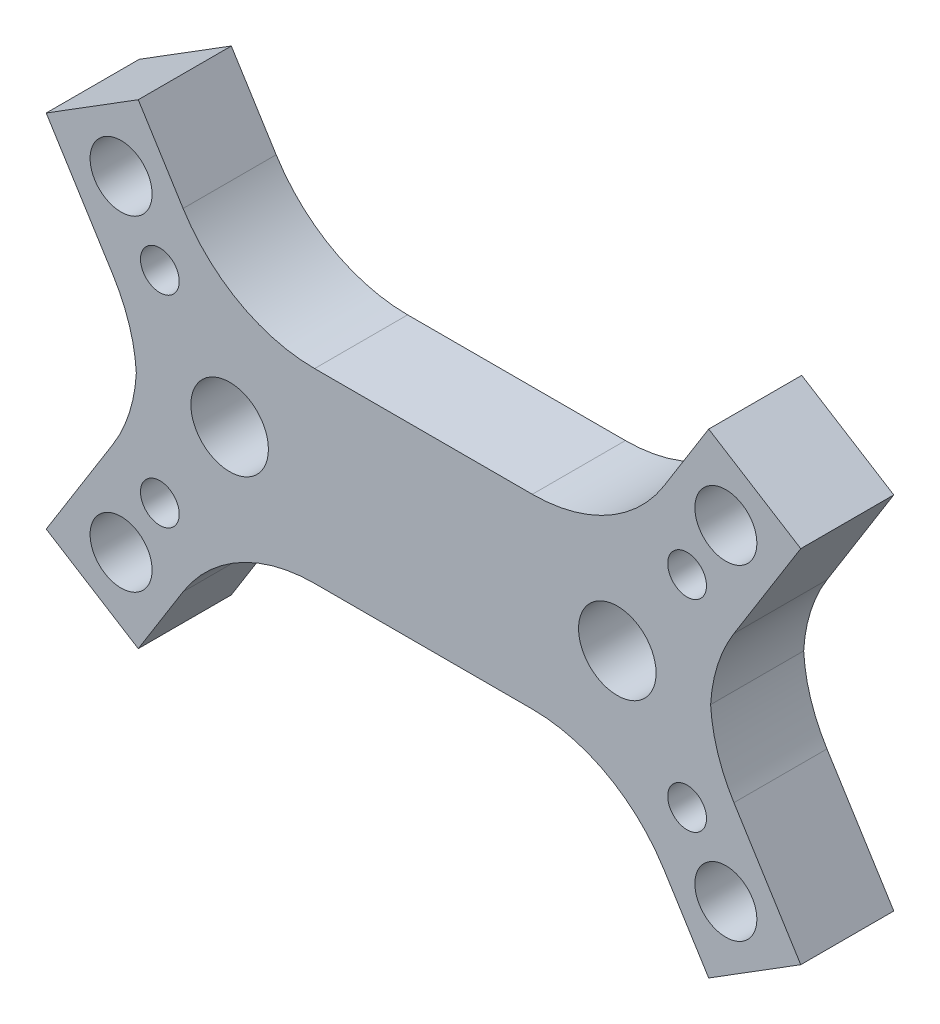
SolidWorks part; units mm, degrees
material "Polyetheretherketone (PEEK)"
ref_plane "Front Plane" through (0, 0, 0) normal (0, 0, 1) x (1, 0, 0)
ref_plane "Top Plane" through (0, 0, 0) normal (0, 1, 0) x (1, 0, 0)
ref_plane "Right Plane" through (0, 0, 0) normal (1, 0, 0) x (0, 0, -1)
ref_plane "Plane1" through (0, 0, 1.2) normal (0, 0, 1) x (1, 0, 0)
sketch "Sketch1" plane through (0, 0, 1.2) normal (0, 0, 1) x (1, 0, 0)
  line L0 (7.4, 2.4) -> (0, 2.4)
  line L1 (0, 2.4) -> (0, 0)
  line L2 (0, 0) -> (7.4, 0)
  line L3 (7.4, 0) -> (7.4, 2.4)
  line L4 (-0.6415, 3.4266) -> (0.6415, 1.3734)
  line L5 (8.1339, 3.5744) -> (6.6661, 1.2256)
  line L6 (0, 1.6581) -> (1.1873, 2.4)
  line L7 (0, 1.6581) -> (-1.1658, 3.5238)
  line L8 (1.1873, 2.4) -> (0.0214, 4.2657)
  line L9 (-1.1658, 3.5238) -> (0.0214, 4.2657)
  line L10 (6.2127, 2.4) -> (7.4, 1.6581)
  line L11 (6.2127, 2.4) -> (7.3786, 4.2657)
  line L12 (7.4, 1.6581) -> (8.5658, 3.5238)
  line L13 (7.3786, 4.2657) -> (8.5658, 3.5238)
  line L14 (0.563, 0.901) -> (0, 0)
  line L15 (7.9999, -0.9601) -> (6.8001, 0.9601)
  line L16 (0, 0.7419) -> (1.1873, 0)
  line L17 (0, 0.7419) -> (-1.1658, -1.1238)
  line L18 (1.1873, 0) -> (0.0214, -1.8657)
  line L19 (-1.1658, -1.1238) -> (0.0214, -1.8657)
  line L20 (6.2127, 0) -> (7.4, 0.7419)
  line L21 (6.2127, 0) -> (7.3786, -1.8657)
  line L22 (7.4, 0.7419) -> (8.5658, -1.1238)
  line L23 (7.3786, -1.8657) -> (8.5658, -1.1238)
  point P7 (0, 2.4)
  point P10 (7.4, 2.4)
  point P22 (0, 0)
  point P25 (7.4, 0)
  dimension "D1" = 2.4
  dimension "D2" = 7.4
  dimension "D3" = 58
  dimension "D4" = 58
  dimension "D5" = 1.4
  dimension "D6" = 2.2
  dimension "D7" = 1.4
  dimension "D8" = 2.2
  dimension "D9" = 58
  dimension "D10" = 58
  dimension "D11" = 2.2
  dimension "D12" = 1.4
  dimension "D13" = 2.2
  dimension "D14" = 1.4
extrude "Boss-Extrude1" add sketch "Sketch1" against normal blind 1.2 contours L9 L7 L1 L0 L8 | L19 L2 L1 | L13 L11 L0 L3 L12 | L21 L23 L22 L3 L2 | L2 L20 L3 L10 L0 L6 L1 | L4 L6 L0 | L1 L6 L4 | L2 | L1 | L20 L2 L15 | L20 L15 L3 | L5 L10 L3 | L0 L10 L5 region at (6.8931, 2.2221, 1.2) region at (7.4535, 3.0969, 1.2) region at (7.2889, 1.9749, 1.2) region at (3.7, 1.2, 1.2) region at (0.5069, 2.2221, 1.2) region at (-0.0535, 3.0969, 1.2) region at (7.4535, -0.6969, 1.2) region at (7.2889, 0.4251, 1.2) region at (0.1111, 1.9749, 1.2) region at (6.8931, 0.1779, 1.2) region at (0.1111, 0.4251, 1.2) region at (-0.0535, -0.6969, 1.2) region at (0.5069, 0.1779, 1.2)
hole_wizard "Hole1" positions "Sketch5" profile "Sketch4" legacy end condition through all
sketch "Sketch5" plane through (0, 0, 1.2) normal (0, 0, 1) x (1, 0, 0)
  point P0 (1.2, 1.2)
  point P1 (6.2, 1.2)
sketch "Sketch4" plane through (1.2, 1.2, 1.2) normal (1, 0, 0) x (0, -1, 0)
  line L0 (0, 0) -> (0, 1.2)
  line L1 (0, 1.2) -> (0.3, 1.2)
  line L2 (0.3, 1.2) -> (0.3, 0.9)
  line L3 (0.3, 0.9) -> (0.5, 0.9)
  line L4 (0.5, 0.9) -> (0.5, 0)
  line L5 (0.5, 0) -> (0, 0)
  line L6 (0, 110) -> (0, -10) construction
  dimension "Diameter" = 0.6
  dimension "Depth" = 1.2
  dimension "C-Bore Diameter" = 1
  dimension "C-Bore Depth" = 0.9
fillet "Fillet1" radius 2 8 edges at (6.2127, 2.4, 0.6) (7.4, 1.6581, 0.6) (7.4, 0.7419, 0.6) (6.2127, 0, 0.6) (1.1873, 0, 0.6) (0, 0.7419, 0.6) (0, 1.6581, 0.6) (1.1873, 2.4, 0.6)
hole_wizard "Ø0.8 (0.8) Diameter Hole1" positions "Sketch7" profile "Sketch6" hole size "Ø0.8" standard "ISO" end condition through all
sketch "Sketch7" plane through (0, 0, 1.2) normal (0, 0, 1) x (1, 0, 0)
  circle A0 centre (1.2, 1.2) radius 0.5 construction
  circle A1 centre (1.2, 1.2) radius 0.5 construction
  circle A2 centre (1.2, 1.2) radius 0.3 construction
  point P0 (-0.2, 3.3)
  point P2 (7.6, 3.3)
  point P11 (-0.2, -0.9)
  point P13 (7.6, -0.9)
  dimension "D1" = 1.4
  dimension "D2" = 2.1
  dimension "D4" = 2.1
  dimension "D3" = 7.8
sketch "Sketch6" plane through (-0.2, 3.3, 1.2) normal (1, 0, 0) x (0, -1, 0)
  line L0 (0, 0) -> (0, 1.2)
  line L1 (0, 1.2) -> (0.4, 1.2)
  line L2 (0.4, 1.2) -> (0.4, 0)
  line L5 (0.4, 0) -> (0, 0)
  line L11 (0, -6.35) -> (0, 107.95) construction
  dimension "Thru Hole Dia." = 0.8
  dimension "Thru Hole Depth" = 1.2
hole_wizard "Ø0.5 (0.5) Diameter Hole1" positions "Sketch9" profile "Sketch8" hole size "Ø0.5" standard "ISO" end condition through all
sketch "Sketch9" plane through (0, 0, 1.2) normal (0, 0, 1) x (1, 0, 0)
  circle A0 centre (1.2, 1.2) radius 0.3 construction
  circle A1 centre (6.2, 1.2) radius 0.3 construction
  point P4 (7.1, -0.1)
  point P6 (0.3, -0.1)
  point P8 (0.3, 2.5)
  point P10 (7.1, 2.5)
  dimension "D1" = 1.3
  dimension "D3" = 1.3
  dimension "D4" = 0.9
  dimension "D2" = 0.9
sketch "Sketch8" plane through (7.1, -0.1, 1.2) normal (1, 0, 0) x (0, -1, 0)
  line L0 (0, 0) -> (0, 1.2)
  line L1 (0, 1.2) -> (0.25, 1.2)
  line L2 (0.25, 1.2) -> (0.25, 0)
  line L5 (0.25, 0) -> (0, 0)
  line L11 (0, -6.35) -> (0, 107.95) construction
  dimension "Thru Hole Dia." = 0.5
  dimension "Thru Hole Depth" = 1.2
